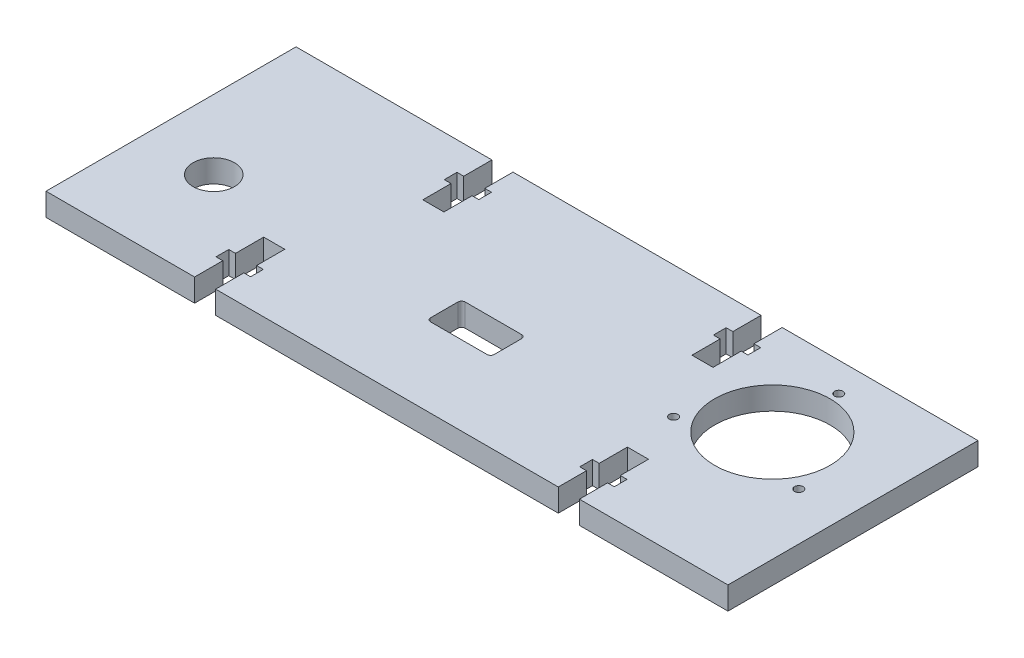
SolidWorks part; units mm, degrees
material "Acrylic (Medium-high impact)"
ref_plane "Front Plane" through (0, 0, 0) normal (0, 0, 1) x (1, 0, 0)
ref_plane "Top Plane" through (0, 0, 0) normal (0, 1, 0) x (1, 0, 0)
ref_plane "Right Plane" through (0, 0, 0) normal (1, 0, 0) x (0, 0, -1)
sketch "Sketch1" plane through (0, 0, 0) normal (0, 1, 0) x (1, 0, 0)
  line L1 (-47.625, -17.4625) -> (47.625, -17.4625)
  line L2 (-47.625, -17.4625) -> (-47.625, 17.4625)
  line L3 (-47.625, 17.4625) -> (47.625, 17.4625)
  line L4 (47.625, -17.4625) -> (47.625, 17.4625)
  line L5 (-47.625, -17.4625) -> (47.625, 17.4625) construction
  line L6 (-47.625, 17.4625) -> (47.625, -17.4625) construction
  point P0 (0, 0)
  dimension "D1" = 95.25
  dimension "D2" = 34.925
extrude "Boss-Extrude1" add sketch "Sketch1" along normal blind 3.175
hole_wizard "Tap Drill for #0-80 Tap1" positions "Sketch2" profile "Sketch3" hole size "#0-80" standard "ANSI Inch" end condition through all
sketch "Sketch2" plane through (0, 3.175, 0) normal (0, 1, 0) x (1, 0, 0)
  point P0 (40.9766, -0.9208)
  point P3 (23.4886, -0.9208)
  point P6 (32.2326, 13.4048)
sketch "Sketch3" plane through (40.9766, 3.175, 0.9208) normal (1, 0, 0) x (0, 0, 1)
  line L0 (0, 0) -> (0, 3.175)
  line L1 (0, 3.175) -> (0.5956, 3.175)
  line L2 (0.5956, 3.175) -> (0.5956, 0)
  line L5 (0.5956, 0) -> (0, 0)
  line L11 (0, -6.35) -> (0, 107.95) construction
  dimension "Thru Hole Dia." = 1.1913
  dimension "Thru Hole Depth" = 3.175
hole_wizard "#12 Clearance Hole1" positions "Sketch4" profile "Sketch5" hole size "#12" standard "ANSI Inch" end condition through all
sketch "Sketch4" plane through (0, 3.175, 0) normal (0, 1, 0) x (1, 0, 0)
  point P0 (-37.9095, -3.7465)
sketch "Sketch5" plane through (-37.9095, 3.175, 3.7465) normal (1, 0, 0) x (0, 0, 1)
  line L0 (0, 0) -> (0, 3.175)
  line L1 (0, 3.175) -> (2.8956, 3.175)
  line L2 (2.8956, 3.175) -> (2.8956, 0)
  line L5 (2.8956, 0) -> (0, 0)
  line L11 (0, -6.35) -> (0, 107.95) construction
  dimension "Thru Hole Dia." = 5.7912
  dimension "Thru Hole Depth" = 3.175
sketch "Sketch6" plane through (0, 3.175, 0) normal (0, 1, 0) x (1, 0, 0)
  line L1 (3.429, -6.4135) -> (-5.461, -6.4135)
  line L2 (3.429, -6.4135) -> (3.429, -1.5875)
  line L3 (3.429, -1.5875) -> (-5.461, -1.5875)
  line L4 (-5.461, -6.4135) -> (-5.461, -1.5875)
extrude "Cut-Extrude1" cut sketch "Sketch6" against normal through all
sketch "Sketch7" plane through (0, 3.175, 0) normal (0, 1, 0) x (1, 0, 0)
  line L0 (47.625, -17.4625) -> (47.625, 17.4625) construction
  line L1 (47.625, -12.5857) -> (42.164, -12.5857)
  line L2 (47.625, -12.5857) -> (47.625, -9.6393)
  line L3 (47.625, -9.6393) -> (42.164, -9.6393)
  line L4 (34.925, -12.5857) -> (34.925, -9.6393)
  line L5 (47.625, -12.5857) -> (34.925, -9.6393) construction
  line L6 (47.625, -11.1125) -> (34.925, -11.1125) construction
  line L7 (-47.625, -17.4625) -> (47.625, -17.4625) construction
  line L8 (47.625, 9.6393) -> (42.164, 9.6393)
  line L9 (42.164, -8.6995) -> (40.386, -8.6995)
  line L10 (42.164, -8.6995) -> (42.164, -9.6393)
  line L11 (42.164, -13.5255) -> (40.386, -13.5255)
  line L12 (40.386, -8.6995) -> (40.386, -9.6393)
  line L13 (42.164, -8.6995) -> (40.386, -13.5255) construction
  line L14 (42.164, -13.5255) -> (40.386, -8.6995) construction
  line L15 (42.164, -12.5857) -> (42.164, -13.5255)
  line L16 (40.386, -9.6393) -> (34.925, -9.6393)
  line L17 (40.386, -12.5857) -> (40.386, -13.5255)
  line L18 (40.386, -12.5857) -> (34.925, -12.5857)
  line L19 (47.625, 9.6393) -> (47.625, 12.5857)
  line L20 (47.625, 12.5857) -> (42.164, 12.5857)
  line L21 (34.925, 9.6393) -> (34.925, 12.5857)
  line L22 (42.164, 13.5255) -> (40.386, 13.5255)
  line L23 (42.164, 13.5255) -> (42.164, 12.5857)
  line L24 (42.164, 8.6995) -> (40.386, 8.6995)
  line L25 (40.386, 13.5255) -> (40.386, 12.5857)
  line L26 (42.164, 9.6393) -> (42.164, 8.6995)
  line L27 (40.386, 12.5857) -> (34.925, 12.5857)
  line L28 (40.386, 9.6393) -> (40.386, 8.6995)
  line L29 (40.386, 9.6393) -> (34.925, 9.6393)
  line L30 (47.625, 9.6393) -> (34.925, 12.5857) construction
  line L31 (47.625, 11.1125) -> (34.925, 11.1125) construction
  line L32 (42.164, 13.5255) -> (40.386, 8.6995) construction
  line L33 (42.164, 8.6995) -> (40.386, 13.5255) construction
  line L34 (0, 0) -> (0, 17.4625) construction
  line L35 (47.625, 17.4625) -> (-47.625, 17.4625) construction
  line L36 (-42.164, 8.6995) -> (-40.386, 13.5255) construction
  line L37 (-42.164, 13.5255) -> (-40.386, 8.6995) construction
  line L38 (-47.625, 11.1125) -> (-34.925, 11.1125) construction
  line L39 (-47.625, 9.6393) -> (-34.925, 12.5857) construction
  line L40 (-42.164, -13.5255) -> (-40.386, -8.6995) construction
  line L41 (-42.164, -8.6995) -> (-40.386, -13.5255) construction
  line L42 (-47.625, -11.1125) -> (-34.925, -11.1125) construction
  line L43 (-47.625, -12.5857) -> (-34.925, -9.6393) construction
  line L44 (-40.386, 9.6393) -> (-34.925, 9.6393)
  line L45 (-40.386, 9.6393) -> (-40.386, 8.6995)
  line L46 (-40.386, 12.5857) -> (-34.925, 12.5857)
  line L47 (-42.164, 9.6393) -> (-42.164, 8.6995)
  line L48 (-40.386, 13.5255) -> (-40.386, 12.5857)
  line L49 (-42.164, 8.6995) -> (-40.386, 8.6995)
  line L50 (-42.164, 13.5255) -> (-42.164, 12.5857)
  line L51 (-42.164, 13.5255) -> (-40.386, 13.5255)
  line L52 (-34.925, 9.6393) -> (-34.925, 12.5857)
  line L53 (-47.625, 12.5857) -> (-42.164, 12.5857)
  line L54 (-47.625, 9.6393) -> (-47.625, 12.5857)
  line L55 (-40.386, -12.5857) -> (-34.925, -12.5857)
  line L56 (-40.386, -12.5857) -> (-40.386, -13.5255)
  line L57 (-40.386, -9.6393) -> (-34.925, -9.6393)
  line L58 (-42.164, -12.5857) -> (-42.164, -13.5255)
  line L59 (-40.386, -8.6995) -> (-40.386, -9.6393)
  line L60 (-42.164, -13.5255) -> (-40.386, -13.5255)
  line L61 (-42.164, -8.6995) -> (-42.164, -9.6393)
  line L62 (-42.164, -8.6995) -> (-40.386, -8.6995)
  line L63 (-47.625, 9.6393) -> (-42.164, 9.6393)
  line L64 (-34.925, -12.5857) -> (-34.925, -9.6393)
  line L65 (-47.625, -9.6393) -> (-42.164, -9.6393)
  line L66 (-47.625, -12.5857) -> (-47.625, -9.6393)
  line L67 (-47.625, -12.5857) -> (-42.164, -12.5857)
  point P10 (41.275, -11.1125)
  point P26 (41.275, 11.1125)
  point P67 (-41.275, 11.1125)
  point P68 (-41.275, -11.1125)
  dimension "D1" = 6.35
  dimension "D2" = 2.9464
  dimension "D3" = 12.7
  dimension "D4" = 1.778
  dimension "D5" = 4.826
  dimension "D6" = 2
extrude "Cut-Extrude2" [suppressed] cut sketch "Sketch7" against normal through all
sketch "Sketch8" plane through (0, 3.175, 0) normal (0, 1, 0) x (1, 0, 0)
  line L0 (-47.625, -17.4625) -> (47.625, -17.4625) construction
  line L1 (23.9268, -17.4625) -> (26.8732, -17.4625)
  line L2 (23.9268, -17.4625) -> (23.9268, -13.5255)
  line L3 (23.9268, -7.8105) -> (26.8732, -7.8105)
  line L4 (26.8732, -17.4625) -> (26.8732, -13.5255)
  line L5 (25.4, -17.4625) -> (25.4, -7.8105) construction
  line L6 (23.9268, -13.5255) -> (22.987, -13.5255)
  line L7 (27.813, -11.7475) -> (26.8732, -11.7475)
  line L8 (27.813, -11.7475) -> (27.813, -13.5255)
  line L9 (27.813, -13.5255) -> (26.8732, -13.5255)
  line L10 (22.987, -11.7475) -> (22.987, -13.5255)
  line L11 (27.813, -11.7475) -> (22.987, -13.5255) construction
  line L12 (27.813, -13.5255) -> (22.987, -11.7475) construction
  line L13 (26.8732, -11.7475) -> (26.8732, -7.8105)
  line L14 (23.9268, -11.7475) -> (22.987, -11.7475)
  line L15 (23.9268, -11.7475) -> (23.9268, -7.8105)
  line L16 (-26.8732, -17.4625) -> (-23.9268, -17.4625)
  line L17 (-26.8732, -17.4625) -> (-26.8732, -13.5255)
  line L18 (-26.8732, -7.8105) -> (-23.9268, -7.8105)
  line L19 (-23.9268, -17.4625) -> (-23.9268, -13.5255)
  line L20 (-26.8732, -13.5255) -> (-27.813, -13.5255)
  line L21 (-22.987, -11.7475) -> (-23.9268, -11.7475)
  line L22 (-22.987, -11.7475) -> (-22.987, -13.5255)
  line L23 (-22.987, -13.5255) -> (-23.9268, -13.5255)
  line L24 (-27.813, -11.7475) -> (-27.813, -13.5255)
  line L25 (-23.9268, -11.7475) -> (-23.9268, -7.8105)
  line L26 (-26.8732, -11.7475) -> (-27.813, -11.7475)
  line L27 (-26.8732, -11.7475) -> (-26.8732, -7.8105)
  line L28 (-25.4, -17.4625) -> (-25.4, -7.8105) construction
  line L29 (-22.987, -11.7475) -> (-27.813, -13.5255) construction
  line L30 (-22.987, -13.5255) -> (-27.813, -11.7475) construction
  line L31 (0, 0) -> (-7.905, 0) construction
  line L32 (-22.987, 13.5255) -> (-27.813, 11.7475) construction
  line L33 (-22.987, 11.7475) -> (-27.813, 13.5255) construction
  line L34 (-25.4, 17.4625) -> (-25.4, 7.8105) construction
  line L35 (27.813, 13.5255) -> (22.987, 11.7475) construction
  line L36 (27.813, 11.7475) -> (22.987, 13.5255) construction
  line L37 (25.4, 17.4625) -> (25.4, 7.8105) construction
  line L38 (-26.8732, 11.7475) -> (-26.8732, 7.8105) construction
  line L39 (-26.8732, 11.7475) -> (-27.813, 11.7475) construction
  line L40 (-23.9268, 11.7475) -> (-23.9268, 7.8105) construction
  line L41 (-27.813, 11.7475) -> (-27.813, 13.5255) construction
  line L42 (-22.987, 13.5255) -> (-23.9268, 13.5255) construction
  line L43 (-22.987, 11.7475) -> (-22.987, 13.5255) construction
  line L44 (-22.987, 11.7475) -> (-23.9268, 11.7475) construction
  line L45 (-26.8732, 13.5255) -> (-27.813, 13.5255) construction
  line L46 (-23.9268, 17.4625) -> (-23.9268, 13.5255) construction
  line L47 (-26.8732, 7.8105) -> (-23.9268, 7.8105) construction
  line L48 (-26.8732, 17.4625) -> (-26.8732, 13.5255) construction
  line L49 (-26.8732, 17.4625) -> (-23.9268, 17.4625) construction
  line L50 (23.9268, 11.7475) -> (23.9268, 7.8105) construction
  line L51 (23.9268, 11.7475) -> (22.987, 11.7475) construction
  line L52 (26.8732, 11.7475) -> (26.8732, 7.8105) construction
  line L53 (22.987, 11.7475) -> (22.987, 13.5255) construction
  line L54 (27.813, 13.5255) -> (26.8732, 13.5255) construction
  line L55 (27.813, 11.7475) -> (27.813, 13.5255) construction
  line L56 (27.813, 11.7475) -> (26.8732, 11.7475) construction
  line L57 (23.9268, 13.5255) -> (22.987, 13.5255) construction
  line L58 (26.8732, 17.4625) -> (26.8732, 13.5255) construction
  line L59 (23.9268, 7.8105) -> (26.8732, 7.8105) construction
  line L60 (23.9268, 17.4625) -> (23.9268, 13.5255) construction
  line L61 (23.9268, 17.4625) -> (26.8732, 17.4625) construction
  line L63 (17.3228, 11.7475) -> (17.3228, 7.8105)
  line L64 (17.3228, 11.7475) -> (16.383, 11.7475)
  line L65 (20.2692, 11.7475) -> (20.2692, 7.8105)
  line L66 (16.383, 11.7475) -> (16.383, 13.5255)
  line L67 (21.209, 13.5255) -> (20.2692, 13.5255)
  line L68 (21.209, 11.7475) -> (21.209, 13.5255)
  line L69 (21.209, 11.7475) -> (20.2692, 11.7475)
  line L70 (17.3228, 13.5255) -> (16.383, 13.5255)
  line L71 (20.2692, 17.4625) -> (20.2692, 13.5255)
  line L72 (17.3228, 7.8105) -> (20.2692, 7.8105)
  line L73 (17.3228, 17.4625) -> (17.3228, 13.5255)
  line L74 (17.3228, 17.4625) -> (20.2692, 17.4625)
  line L75 (21.209, 13.5255) -> (16.383, 11.7475) construction
  line L76 (21.209, 11.7475) -> (16.383, 13.5255) construction
  line L77 (18.796, 17.4625) -> (18.796, 7.8105) construction
  line L78 (-20.2692, 11.7475) -> (-20.2692, 7.8105)
  line L79 (-20.2692, 11.7475) -> (-21.209, 11.7475)
  line L80 (-17.3228, 11.7475) -> (-17.3228, 7.8105)
  line L81 (-21.209, 11.7475) -> (-21.209, 13.5255)
  line L82 (-16.383, 13.5255) -> (-17.3228, 13.5255)
  line L83 (-16.383, 11.7475) -> (-16.383, 13.5255)
  line L84 (-16.383, 11.7475) -> (-17.3228, 11.7475)
  line L85 (-20.2692, 13.5255) -> (-21.209, 13.5255)
  line L86 (-17.3228, 17.4625) -> (-17.3228, 13.5255)
  line L87 (-20.2692, 7.8105) -> (-17.3228, 7.8105)
  line L88 (-20.2692, 17.4625) -> (-20.2692, 13.5255)
  line L89 (-20.2692, 17.4625) -> (-17.3228, 17.4625)
  line L90 (-16.383, 13.5255) -> (-21.209, 11.7475) construction
  line L91 (-16.383, 11.7475) -> (-21.209, 13.5255) construction
  line L92 (-18.796, 17.4625) -> (-18.796, 7.8105) construction
  point P8 (25.4, -12.6365)
  point P25 (-25.4, -12.6365)
  point P63 (-25.4, 12.6365)
  point P64 (25.4, 12.6365)
  point P80 (18.796, 12.6365)
  point P95 (-18.796, 12.6365)
  dimension "D1" = 25.4
  dimension "D2" = 9.652
  dimension "D3" = 1.778
  dimension "D4" = 4.826
  dimension "D5" = 2.9464
  dimension "D6" = 2
  dimension "D7" = 2
  dimension "D8" = 2
extrude "Cut-Extrude3" cut sketch "Sketch8" against normal through all
sketch "Sketch9" plane through (0, 3.175, 0) normal (0, 1, 0) x (1, 0, 0)
  circle A0 centre (32.2326, 4.1275) radius 8.0645
  dimension "D1" = 16.129
extrude "Cut-Extrude4" cut sketch "Sketch9" against normal through all
fillet "Fillet1" radius 0.508 4 edges at (3.429, 1.5875, 1.5875) (-5.461, 1.5875, 1.5875) (-5.461, 1.5875, 6.4135) (3.429, 1.5875, 6.4135)
equation "\"#4D\"= .116'slot for adding a #4 screw"
equation "\"D5@Sketch8\"=\"#4D\""
equation "\"#4H\"= .38'slot heigth for adding a #4 screw with 1/2\" length"
equation "\"mat\"= 1 / 8'thickness of material"
equation "\"D2@Sketch8\"=\"#4H\""
equation "\"D1@Boss-Extrude1\"=\"mat\""
